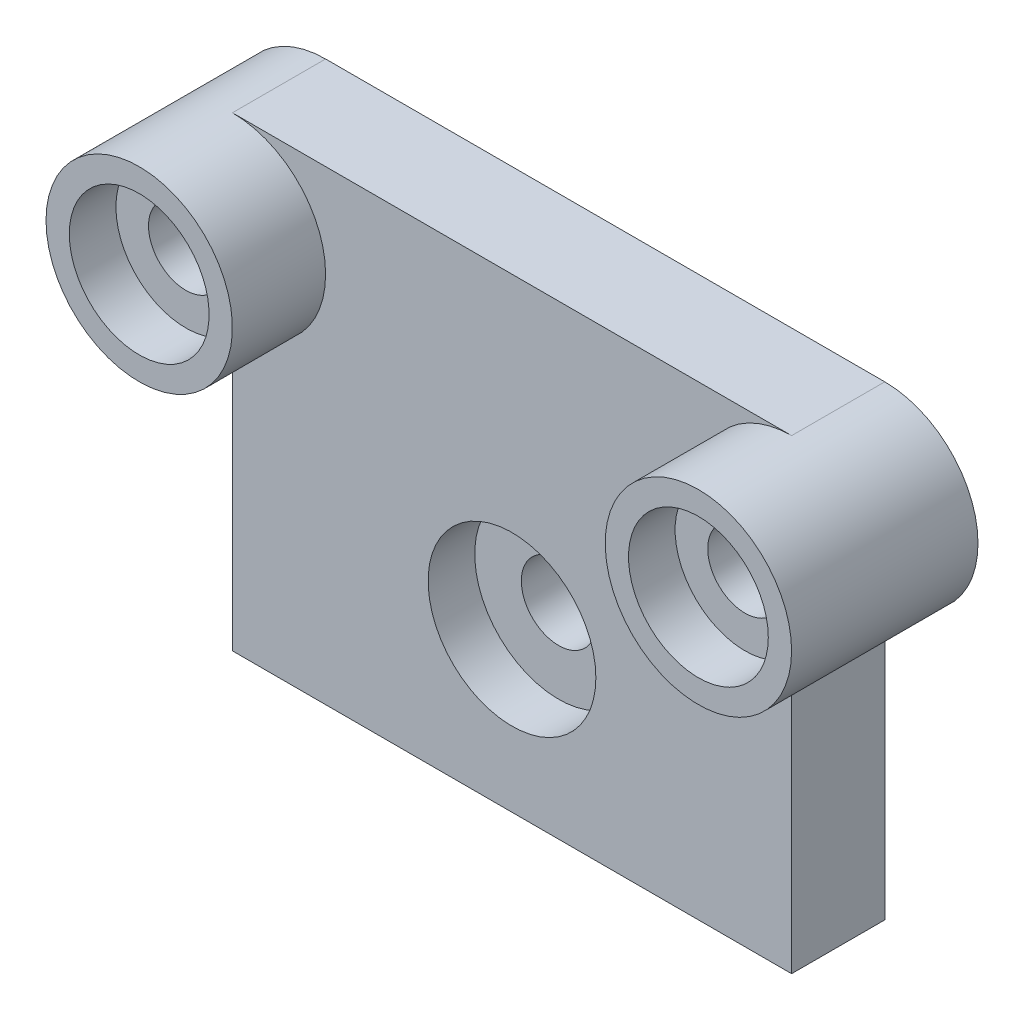
SolidWorks part; units mm, degrees
ref_plane "Спереди" through (0, 0, 0) normal (0, 0, 1) x (1, 0, 0)
ref_plane "Сверху" through (0, 0, 0) normal (0, 1, 0) x (1, 0, 0)
ref_plane "Справа" through (0, 0, 0) normal (1, 0, 0) x (0, 0, -1)
sketch "Эскиз1" plane through (0, 0, 0) normal (0, 0, 1) x (1, 0, 0)
  line L1 (-15, -25) -> (15, -25)
  line L2 (-15, -25) -> (-15, 25)
  line L3 (-15, 25) -> (15, 25)
  line L4 (15, -25) -> (15, 25)
  line L5 (-15, -25) -> (15, 25) construction
  line L6 (-15, 25) -> (15, -25) construction
  circle A0 centre (-15, -8) radius 4
  circle A1 centre (-15, -8) radius 8
  circle A2 centre (15, 15) radius 10
  circle A3 centre (15, 15) radius 4
  point P0 (0, 0)
  dimension "D3" = 8
  dimension "D5" = 16
  dimension "D6" = 20
  dimension "D7" = 8
  dimension "D1" = 30
  dimension "D2" = 50
  dimension "D4" = 17
extrude "Бобышка-Вытянуть1" add sketch "Эскиз1" along normal blind 10 contours A2 L3 L2 A1 L1 L4 | L2 A1 A0 | A3 L4 A2 | A3 L4 A2 region at (-0.4209, -1.2492, 0) region at (-14.8211, -14, 0) region at (10.2708, 15, 0) region at (19.7292, 15, 0)
extrude "Бобышка-Вытянуть2" add sketch "Эскиз1<3>" along normal blind 20 contours A3 L4 A2 | A3 L4 A2 region at (10.2708, 15, 0) region at (19.7292, 15, 0)
sketch "Эскиз1<3>" plane through (0, 0, 0) normal (0, 0, 1) x (1, 0, 0) same geometry as "Эскиз1"
sketch "Эскиз3" plane through (0, 0, 20) normal (0, 0, 1) x (1, 0, 0)
  circle A0 centre (15, 15) radius 7.5
  dimension "D1" = 15
extrude "Вырез-Вытянуть1" cut sketch "Эскиз3" against normal blind 5
sketch "Эскиз4" plane through (0, 0, 20) normal (0, 0, 1) x (1, 0, 0)
  line L0 (25, 15) -> (5, 15) construction
  circle A0 centre (15, 15) radius 10 construction
  arc A1 (15, 25) -> (15, 5) centre (15, 15) ccw construction
ref_plane "Плоскость1" through (0, 15, 0) normal (0, 1, 0) x (1, 0, 0)
mirror "Зеркальное отражение1" about plane through (-15, 0, 10) normal (-1, 0, 0) of "Вырез-Вытянуть1", "Бобышка-Вытянуть2", "Бобышка-Вытянуть1"
sketch "Эскиз6" plane through (0, 0, 10) normal (0, 0, 1) x (1, 0, 0)
  circle A0 centre (-15, -8) radius 9
  dimension "D1" = 18
extrude "Вырез-Вытянуть2" cut sketch "Эскиз6" against normal blind 5
